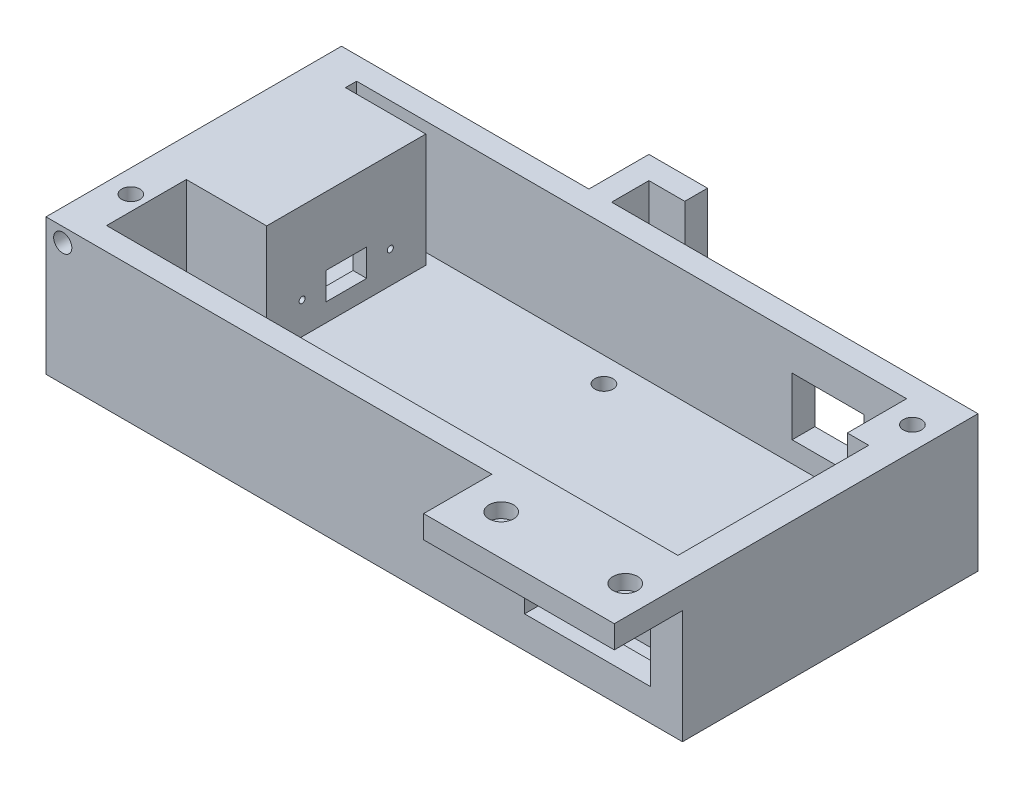
SolidWorks part; units mm, degrees
ref_plane "Front Plane" through (0, 0, 0) normal (0, 0, 1) x (1, 0, 0)
ref_plane "Top Plane" through (0, 0, 0) normal (0, 1, 0) x (1, 0, 0)
ref_plane "Right Plane" through (0, 0, 0) normal (1, 0, 0) x (0, 0, -1)
sketch "Sketch1" plane through (0, 0, 0) normal (0, 1, 0) x (1, 0, 0)
  line L1 (-73.3262, 17.2857) -> (60.6738, 17.2857)
  line L2 (-73.3262, 17.2857) -> (-73.3262, -37.7143)
  line L3 (-73.3262, -37.7143) -> (60.6738, -37.7143)
  line L4 (60.6738, 17.2857) -> (60.6738, -37.7143)
  dimension "D1" = 134
  dimension "D2" = 55
extrude "Boss-Extrude1" add sketch "Sketch1" along normal blind 5
sketch "Sketch2" plane through (0, 5, 0) normal (0, 1, 0) x (1, 0, 0)
  line L5 (-73.3262, -10.2143) -> (-72.321, -10.2143) construction
  line L6 (-73.3262, 11.8283) -> (-50.3262, 11.8283)
  line L7 (-73.3262, -10.2143) -> (-73.3262, -17.1717)
  line L8 (-73.3262, -17.1717) -> (-50.3262, -17.1717)
  line L9 (-50.3262, 11.8283) -> (-50.3262, -17.1717)
  line L11 (-73.3262, 17.2857) -> (-73.3262, -37.7143) construction
  line L12 (-73.3262, -10.2143) -> (-68.3923, -10.2143) construction
  line L13 (-73.3262, 14.8283) -> (-47.3262, 14.8283)
  line L14 (-47.3262, 14.8283) -> (-47.3262, -20.1717)
  line L15 (-47.3262, -20.1717) -> (-73.3262, -20.1717)
  line L16 (-73.3262, -20.1717) -> (-73.3262, -17.1717)
  line L17 (-73.3262, 11.8283) -> (-73.3262, 14.8283)
  line M11 (-73.3262, 17.2857) -> (-73.3262, -37.7143)
  dimension "D1" = 29
  dimension "D2" = 23
  dimension "D3" = 0
  dimension "D4" = 0
  dimension "D5" = 3
  dimension "D6" = 3
  dimension "D7" = 3
extrude "Boss-Extrude2" add sketch "Sketch2" along normal blind 14 contours L15 L14 L13 L6 L9 L8 M11
sketch "Sketch6" plane through (0, 5, 0) normal (0, 1, 0) x (1, 0, 0)
  line L0 (14.1109, 16.8244) -> (16.0963, 16.8244)
  line L1 (-5.1438, 13.8244) -> (15.3701, 13.8244)
  line L2 (-10.1438, -19.1756) -> (49.8562, -19.1756)
  line L3 (-7.1438, 11.8244) -> (-7.1438, 5.8993)
  circle A0 centre (-5.1438, 11.8244) radius 2
  line M9 (60.6738, -37.7143) -> (60.6738, 17.2857)
  dimension "D1" = 4
  dimension "D2" = 3
  dimension "D3" = 36
  dimension "D4" = 60
  dimension "D5" = 3
extrude "Cut-Extrude2" cut sketch "Sketch6" against normal blind 16 contours A0 M9
sketch "Sketch7" plane through (0, 5, 0) normal (0, 1, 0) x (1, 0, 0)
  line L0 (-9.5726, -29.1756) -> (12.8573, -29.1756)
  line L1 (-9.5726, -29.1756) -> (-9.5726, -33.2583)
  line L2 (-9.5726, -33.2583) -> (50.4274, -33.2583)
  line L3 (12.8573, -29.1756) -> (50.4274, -29.1756)
  line L4 (50.4274, -29.1756) -> (50.4274, -33.2583)
  circle A0 centre (-5.1438, 11.8244) radius 2 construction
  dimension "D1" = 41
  dimension "D2" = 60
extrude "Boss-Extrude4" add sketch "Sketch7" along normal blind 10
sketch "Sketch8" plane through (0, 5, 0) normal (0, 1, 0) x (1, 0, 0)
  circle A0 centre (46.7261, 11.8244) radius 1.5
  dimension "D1" = 3
extrude "Boss-Extrude5" add sketch "Sketch8" along normal blind 6
sketch "Sketch9" plane through (-50.3262, 0, 0) normal (-1, 0, 0) x (0, 0, 1)
  line L0 (2.6717, 12) -> (0.7864, 12) construction
  line L1 (-11.8283, 5) -> (17.1717, 5) construction
  line L2 (-1.8283, 15) -> (7.1717, 15)
  line L3 (-1.8283, 15) -> (-1.8283, 9)
  line L4 (-1.8283, 9) -> (7.1717, 9)
  line L5 (7.1717, 15) -> (7.1717, 9)
  line L6 (2.6717, 5) -> (2.6717, 10.3562) construction
  line L7 (2.6717, 9) -> (2.6717, 7.6781) construction
  line L8 (11.705, 12) -> (11.705, 10.6987) construction
  line L9 (16.2383, 15) -> (16.2383, 9)
  circle A0 centre (12.3717, 12) radius 0.6667
  circle A1 centre (-7.0283, 12) radius 0.6667
  dimension "D1" = 3
  dimension "D2" = 7
  dimension "D3" = 3
  dimension "D4" = 9
  dimension "D5" = 0
  dimension "D6" = 5.2
extrude "Cut-Extrude3" cut sketch "Sketch9" against normal blind 6 contours L5 L2 L3 L4 | A1 | A0
sketch "Sketch10" plane through (0, 0, 0) normal (0, 1, 0) x (1, 0, 0)
  line L0 (-73.3262, 17.2857) -> (-73.3262, 22.2857)
  line L1 (-73.3262, 22.2857) -> (66.6738, 22.2857)
  line L2 (66.6738, 22.2857) -> (66.6738, -42.7143)
  line L3 (66.6738, -42.7143) -> (-73.3262, -42.7143)
  line L4 (-73.3262, -42.7143) -> (-73.3262, -37.7143)
  line L5 (-73.3262, -37.7143) -> (60.6738, -37.7143)
  line L6 (60.6738, -37.7143) -> (60.6738, 17.2857)
  line L7 (60.6738, 17.2857) -> (-73.3262, 17.2857)
  dimension "D1" = 140
  dimension "D2" = 5
  dimension "D3" = 5
extrude "Boss-Extrude6" add sketch "Sketch10" along normal blind 30
sketch "Sketch11" plane through (0, 19, 0) normal (0, 1, 0) x (1, 0, 0)
  line L1 (-73.3262, 14.8283) -> (-47.3262, 14.8283)
  line L2 (-73.3262, 14.8283) -> (-73.3262, -20.1717)
  line L3 (-73.3262, -20.1717) -> (-47.3262, -20.1717)
  line L4 (-47.3262, 14.8283) -> (-47.3262, -20.1717)
extrude "Boss-Extrude7" add sketch "Sketch11" along normal up to surface (11 mm away) up to face at (-4.8262, 30, 10.2143)
sketch "Sketch12" plane through (0, 5, 0) normal (0, 1, 0) x (1, 0, 0)
  line L0 (-40.8686, -32.1165) -> (-23.8686, -32.1165) construction
  circle A0 centre (-40.8686, -32.1165) radius 2
  circle A1 centre (-23.8686, -32.1165) radius 2
  dimension "D1" = 4
  dimension "D2" = 4
  dimension "D3" = 17
extrude "Cut-Extrude4" cut sketch "Sketch12" against normal through all
sketch "Sketch13" plane through (-73.3262, 0, 0) normal (-1, 0, 0) x (0, 0, 1)
  line L1 (17.1717, 19) -> (-11.8283, 19)
  line L2 (17.1717, 19) -> (17.1717, 20)
  line L3 (17.1717, 20) -> (-11.8283, 20)
  line L4 (-11.8283, 19) -> (-11.8283, 20)
  dimension "D1" = 1
extrude "Cut-Extrude5" cut sketch "Sketch13" against normal up to surface (23 mm away) up to face at (-50.3262, 12, 13.0383)
sketch "Sketch14" plane through (0, 0, 0) normal (0, -1, 0) x (1, 0, 0)
  line L0 (66.6738, -22.2857) -> (-73.3262, -22.2857) construction
  line L1 (-13.9144, -22.2857) -> (46.6519, -22.2857)
  line L3 (-13.9144, -17.2857) -> (46.6519, -17.2857)
  line L4 (46.6519, -22.2857) -> (46.6519, -17.2857)
  line L5 (-13.9144, -22.2857) -> (-13.9144, -30.4917) construction
  line L6 (-13.9144, -22.2857) -> (-18.9144, -22.2857)
  line L7 (-18.9144, -22.2857) -> (-18.9144, -17.2857)
  line L8 (-18.9144, -17.2857) -> (-13.9144, -17.2857)
  dimension "D1" = 5
  dimension "D2" = 5
extrude "Boss-Extrude8" add sketch "Sketch14" along normal blind 12
sketch "Sketch15" plane through (0, 0, -22.2857) normal (0, 0, -1) x (-1, 0, 0)
  line L0 (6.0333, -12) -> (6.0333, -5.6821)
  line L1 (18.9144, -12) -> (-46.6519, -12) construction
  line L2 (13.9144, -5.6821) -> (4.7629, -5.6821) construction
  line L3 (6.0333, -5.6821) -> (13.9144, -5.6821)
  line L4 (13.9144, -5.6821) -> (13.9144, -12)
  line L5 (13.9144, -12) -> (6.0333, -12)
extrude "Boss-Extrude9" add sketch "Sketch15" along normal up to surface (8.206 mm away)
sketch "Sketch17" plane through (0, 0, -22.2857) normal (0, 0, -1) x (-1, 0, 0)
  line L0 (-66.6738, 30) -> (73.3262, 30) construction
  line L1 (13.9144, -12) -> (18.9144, -12)
  line L2 (13.9144, -12) -> (13.9144, 30)
  line L3 (13.9144, 30) -> (18.9144, 30)
  line L4 (18.9144, -12) -> (18.9144, 30)
extrude "Boss-Extrude10" add sketch "Sketch17" along normal up to surface (8.206 mm away) up to face at (-9.9738, -8.8411, -30.4917)
sketch "Sketch18" plane through (0, 0, 42.7143) normal (0, 0, 1) x (1, 0, 0)
  line L1 (31.9361, 7) -> (59.6738, 7)
  line L2 (31.9361, 7) -> (31.9361, 18)
  line L3 (31.9361, 18) -> (59.6738, 18)
  line L4 (59.6738, 7) -> (59.6738, 18)
extrude "Cut-Extrude6" cut sketch "Sketch18" against normal up to surface (5 mm away) up to face at (-6.3262, 17.5, 37.7143)
sketch "Sketch19" plane through (0, 5, 0) normal (0, 1, 0) x (1, 0, 0)
  line L0 (-47.3262, -20.1717) -> (-73.3262, -20.1717) construction
  line L1 (-73.3262, -37.7143) -> (-65.0045, -37.7143)
  line L2 (-73.3262, -37.7143) -> (-73.3262, -20.1717)
  line L3 (-73.3262, -20.1717) -> (-65.0045, -20.1717)
  line L4 (-65.0045, -37.7143) -> (-65.0045, -20.1717)
  line L5 (-73.3262, 14.8283) -> (-47.3262, 14.8283) construction
  line L6 (-65.0045, 14.8283) -> (-73.3262, 14.8283)
  line L7 (-65.0045, 14.8283) -> (-65.0045, 17.2857)
  line L8 (-65.0045, 17.2857) -> (-73.3262, 17.2857)
  line L9 (-73.3262, 14.8283) -> (-73.3262, 17.2857)
extrude "Boss-Extrude11" add sketch "Sketch19" along normal up to surface (25 mm away) up to face at (-60.3262, 30, 2.6717)
sketch "Sketch21" plane through (0, 0, 42.7143) normal (0, 0, 1) x (1, 0, 0)
  line L1 (24.7379, 25) -> (66.6738, 25)
  line L2 (24.7379, 25) -> (24.7379, 30)
  line L3 (24.7379, 30) -> (66.6738, 30)
  line L4 (66.6738, 25) -> (66.6738, 30)
extrude "Boss-Extrude12" add sketch "Sketch21" along normal blind 15
sketch "Sketch22" plane through (0, 30, 0) normal (0, 1, 0) x (1, 0, 0)
  circle A1 centre (32.9393, -48.8506) radius 2.7
  circle A3 centre (60.2285, -48.8506) radius 2.7
  dimension "D2" = 5.4
  dimension "D4" = 5.4
extrude "Cut-Extrude7" cut sketch "Sketch22" against normal blind 3.2
sketch "Sketch23" plane through (0, 30, 0) normal (0, 1, 0) x (1, 0, 0)
  circle A0 centre (60.2285, -48.8506) radius 1.5
  circle A1 centre (32.9393, -48.8506) radius 1.5
  dimension "D1" = 3
  dimension "D2" = 3
extrude "Cut-Extrude8" cut sketch "Sketch23" against normal blind 8.2
sketch "Sketch24" plane through (0, 0, 42.7143) normal (0, 0, 1) x (1, 0, 0)
  circle A0 centre (-69.6433, 26.922) radius 2
  dimension "D1" = 4
extrude "Cut-Extrude9" cut sketch "Sketch24" against normal blind 6.2
sketch "Sketch25" plane through (0, 30, 0) normal (0, 1, 0) x (1, 0, 0)
  circle A1 centre (-68.3013, -29.074) radius 2
  dimension "D1" = 4
extrude "Cut-Extrude10" cut sketch "Sketch25" against normal blind 10.2
sketch "Sketch26" plane through (0, 5, 0) normal (0, 1, 0) x (1, 0, 0)
  line L1 (60.6738, 17.2857) -> (55.97, 17.2857)
  line L2 (60.6738, 17.2857) -> (60.6738, 4.2448)
  line L3 (60.6738, 4.2448) -> (55.97, 4.2448)
  line L4 (55.97, 17.2857) -> (55.97, 4.2448)
extrude "Boss-Extrude13" add sketch "Sketch26" along normal up to vertex (25 mm away)
sketch "Sketch27" plane through (0, 30, 0) normal (0, 1, 0) x (1, 0, 0)
  circle A0 centre (61.5659, 12.966) radius 2
  dimension "D1" = 4
extrude "Cut-Extrude11" cut sketch "Sketch27" against normal blind 11.2
sketch "Sketch28" plane through (0, 0, -30.4917) normal (0, 0, -1) x (-1, 0, 0)
  line L1 (18.9144, 30) -> (6.0333, 30)
  line L2 (18.9144, 30) -> (18.9144, -12)
  line L3 (18.9144, -12) -> (6.0333, -12)
  line L4 (6.0333, 30) -> (6.0333, -12)
extrude "Boss-Extrude14" add sketch "Sketch28" along normal blind 5
sketch "Sketch29" plane through (0, -5.6821, 0) normal (0, 1, 0) x (1, 0, 0)
  circle A0 centre (-9.9738, 26.3887) radius 1.5
  dimension "D1" = 3
extrude "Cut-Extrude12" cut sketch "Sketch29" against normal blind 7
sketch "Sketch30" plane through (0, -12, 0) normal (0, -1, 0) x (1, 0, 0)
  circle A0 centre (-9.9738, -26.3887) radius 2.75
  dimension "D1" = 5.5
extrude "Cut-Extrude13" cut sketch "Sketch30" against normal blind 3
sketch "Sketch31" plane through (0, 0, -22.2857) normal (0, 0, -1) x (-1, 0, 0)
  line L1 (-46.6519, 9.5935) -> (-30.7956, 9.5935)
  line L2 (-46.6519, 9.5935) -> (-46.6519, 22.2935)
  line L3 (-46.6519, 22.2935) -> (-30.7956, 22.2935)
  line L4 (-30.7956, 9.5935) -> (-30.7956, 22.2935)
extrude "Cut-Extrude14" cut sketch "Sketch31" against normal blind 8
fillet "Fillet1" radius 10 1 edges at (13.8687, 0, -17.2857)
fillet "Fillet2" radius 10 1 edges at (-18.9144, 0, -14.7857)
fillet "Fillet3" radius 10 1 edges at (46.6519, 0, -14.7857)
sketch "Sketch32" plane through (-73.3262, 0, 0) normal (-1, 0, 0) x (0, 0, 1)
  line L0 (-1.8283, 12) -> (-22.2857, 12) construction
  line L1 (-1.8283, 15) -> (-1.8283, 9) construction
  line L2 (-22.2857, 30) -> (-22.2857, 0) construction
sketch "Sketch33" plane through (0, 0, -22.2857) normal (0, 0, -1) x (-1, 0, 0)
  line L0 (73.3262, 11.9699) -> (30.1226, 11.9699) construction
  line L1 (73.3262, 30) -> (73.3262, 0) construction
